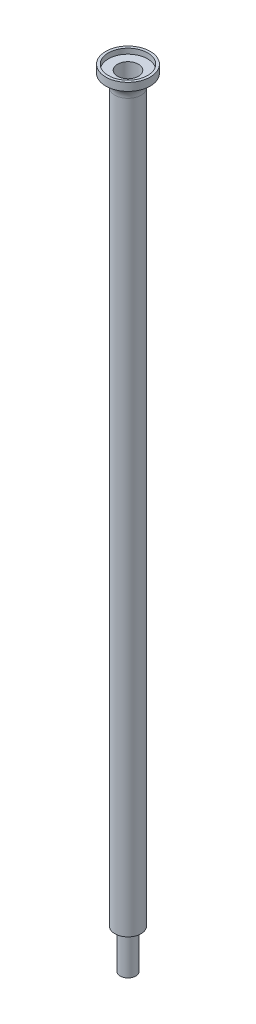
SolidWorks part; units mm, degrees
ref_plane "Front Plane" through (0, 0, 0) normal (0, 0, 1) x (1, 0, 0)
ref_plane "Top Plane" through (0, 0, 0) normal (0, 1, 0) x (1, 0, 0)
ref_plane "Right Plane" through (0, 0, 0) normal (1, 0, 0) x (0, 0, -1)
sketch "Sketch1" plane through (0, 0, 0) normal (1, 0, 0) x (0, 0, -1)
  line L0 (0, 68.844) -> (0, -249.3934) construction
  line L1 (0, 64.1903) -> (8.5, 64.1903)
  line L2 (5, 61.1903) -> (5, -220.8097)
  line L3 (8.5, 64.1903) -> (8.5, 61.1903)
  line L4 (8.5, 61.1903) -> (5, 61.1903)
  line L5 (5, -220.8097) -> (3, -220.8097)
  line L6 (3, -220.8097) -> (3, -235.8097)
  line L7 (3, -235.8097) -> (0, -235.8097)
  line L8 (0, 64.1903) -> (0, -235.8097)
  dimension "D1" = 8.5
  dimension "D2" = 5
  dimension "D3" = 3
  dimension "D4" = 285
  dimension "D5" = 2
  dimension "D6" = 15
revolve "Revolve1" add sketch "Sketch1" angle 360 about L0
shell "Shell1" thickness 1 removed face at (0, 64.1903, 8.5)
sketch "Sketch2" plane through (0, -234.8097, 0) normal (0, 1, 0) x (1, 0, 0)
  circle A0 centre (0, 0) radius 2 construction
  circle A1 centre (0, 0) radius 2
extrude "Cut-Extrude1" cut sketch "Sketch2" against normal through all
fillet "Fillet1" radius 5 1 edges at (0, 61.1903, 5)
